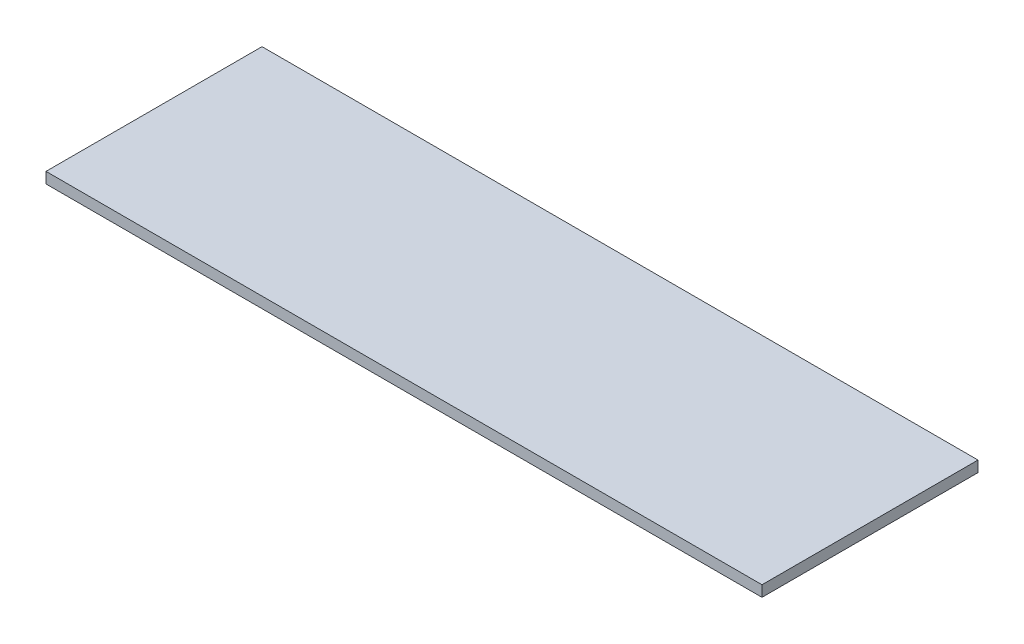
SolidWorks part; units mm, degrees
ref_plane "Front Plane" through (0, 0, 0) normal (0, 0, 1) x (1, 0, 0)
ref_plane "Top Plane" through (0, 0, 0) normal (0, 1, 0) x (1, 0, 0)
ref_plane "Right Plane" through (0, 0, 0) normal (1, 0, 0) x (0, 0, -1)
sketch "Sketch1" plane through (0, 0, 0) normal (0, 1, 0) x (1, 0, 0)
  line L1 (147.5, -44.5) -> (-147.5, -44.5)
  line L2 (147.5, -44.5) -> (147.5, 44.5)
  line L3 (147.5, 44.5) -> (-147.5, 44.5)
  line L4 (-147.5, -44.5) -> (-147.5, 44.5)
  line L5 (147.5, -44.5) -> (-147.5, 44.5) construction
  line L6 (147.5, 44.5) -> (-147.5, -44.5) construction
  point P0 (0, 0)
  dimension "D1" = 295
  dimension "D2" = 89
extrude "Boss-Extrude1" add sketch "Sketch1" along normal blind 4.5
sketch "Sketch2" plane through (0, 4.5, 0) normal (0, 1, 0) x (1, 0, 0)
  line L1 (-147.5, 44.5) -> (-138, 44.5) construction
  line L2 (-147.5, 44.5) -> (-147.5, 35) construction
  line L3 (-147.5, 35) -> (-138, 35) construction
  line L4 (147.5, 44.5) -> (138, 44.5) construction
  line L5 (147.5, 44.5) -> (147.5, 35) construction
  line L6 (147.5, 35) -> (138, 35) construction
  line L7 (138, 44.5) -> (138, 35) construction
  line L8 (-138, 44.5) -> (-138, 35) construction
  circle A0 centre (138, 35) radius 1.6
  circle A1 centre (-138, 35) radius 1.6
  dimension "D3" = 9.5
  dimension "D1" = 9.5
  dimension "D2" = 9.5
  dimension "D4" = 9.5
extrude "Cut-Extrude2" [suppressed] cut sketch "Sketch2" against normal up to next
